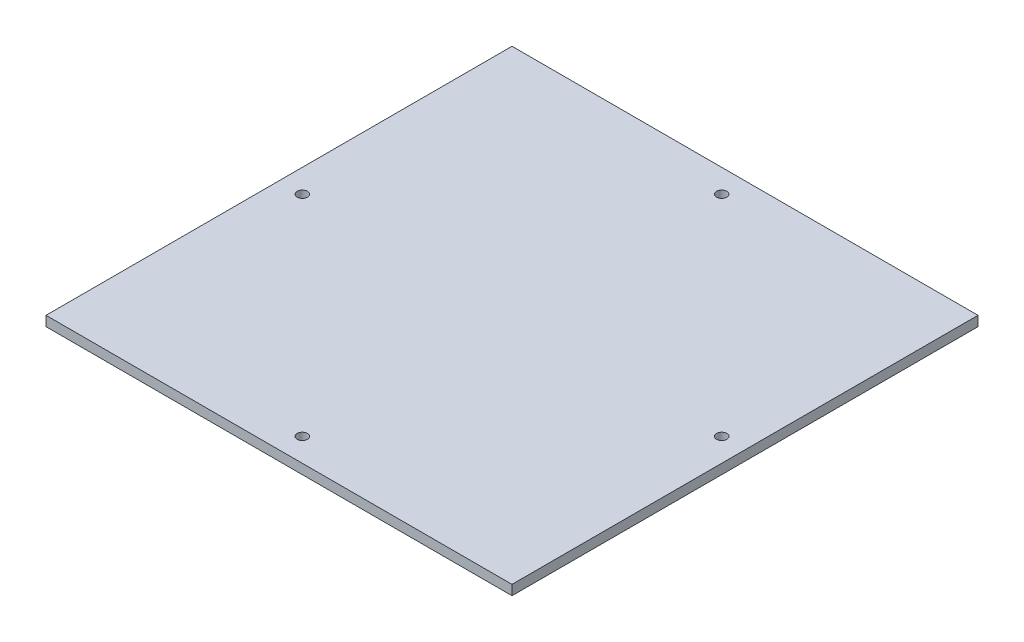
SolidWorks part; units mm, degrees
ref_plane "Front Plane" through (0, 0, 0) normal (0, 0, 1) x (1, 0, 0)
ref_plane "Top Plane" through (0, 0, 0) normal (0, 1, 0) x (1, 0, 0)
ref_plane "Right Plane" through (0, 0, 0) normal (1, 0, 0) x (0, 0, -1)
sketch "Sketch1" plane through (0, 0, 0) normal (0, 1, 0) x (1, 0, 0)
  line L1 (-75, 75) -> (75, 75)
  line L2 (-75, 75) -> (-75, -75)
  line L3 (-75, -75) -> (75, -75)
  line L4 (75, 75) -> (75, -75)
  line L5 (-75, 75) -> (75, -75) construction
  line L6 (-75, -75) -> (75, 75) construction
  line L7 (-67.5, 67.5) -> (67.5, 67.5) construction
  line L8 (-67.5, 67.5) -> (-67.5, -67.5) construction
  line L9 (-67.5, -67.5) -> (67.5, -67.5) construction
  line L10 (67.5, 67.5) -> (67.5, -67.5) construction
  line L11 (-67.5, 67.5) -> (67.5, -67.5) construction
  line L12 (-67.5, -67.5) -> (67.5, 67.5) construction
  circle A0 centre (-67.5, 0) radius 1.65
  circle A1 centre (0, 67.5) radius 1.65
  circle A2 centre (67.5, 0) radius 1.65
  circle A3 centre (0, -67.5) radius 1.65
  point P0 (0, 0)
  point P6 (0, 0)
  dimension "D5" = 3.3
  dimension "D1" = 7.5
  dimension "D2" = 7.5
  dimension "D3" = 150
  dimension "D4" = 150
extrude "Boss-Extrude1" add sketch "Sketch1" along normal blind 3.175
